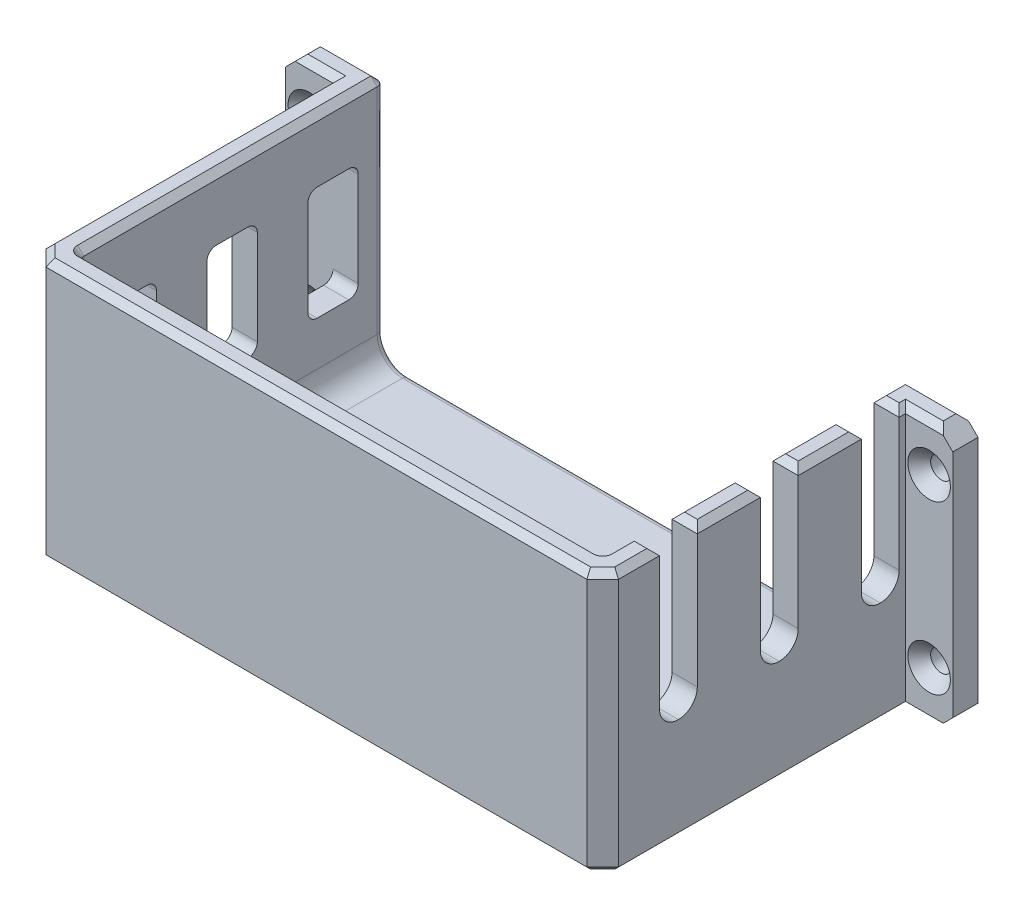
SolidWorks part; units mm, degrees
ref_plane "Front Plane" through (0, 0, 0) normal (0, 0, 1) x (1, 0, 0)
ref_plane "Top Plane" through (0, 0, 0) normal (0, 1, 0) x (1, 0, 0)
ref_plane "Right Plane" through (0, 0, 0) normal (1, 0, 0) x (0, 0, -1)
sketch "Sketch1" plane through (0, 0, 0) normal (0, 1, 0) x (1, 0, 0)
  line L0 (0, 0) -> (-23, 0)
  line L1 (-23, 0) -> (-23, -8)
  line L2 (-23, -8) -> (-8, -8)
  line L3 (-8, -8) -> (-8, -104)
  line L4 (-8, -104) -> (173.5, -104)
  line L5 (173.5, -104) -> (173.5, -8)
  line L6 (173.5, -8) -> (188.5, -8)
  line L7 (188.5, -8) -> (188.5, 0)
  line L8 (188.5, 0) -> (165.5, 0)
  line L9 (165.5, 0) -> (165.5, -96)
  line L10 (165.5, -96) -> (0, -96)
  line L11 (0, -96) -> (0, 0)
  line L12 (165.5, -96) -> (173.5, -96) construction
  line L13 (0, -96) -> (-8, -96) construction
  point P13 (170.5, -72.739)
  dimension "D1" = 8
  dimension "D2" = 165.5
  dimension "D3" = 8
  dimension "D4" = 15
  dimension "D5" = 8
  dimension "D6" = 96
extrude "Boss-Extrude1" add sketch "Sketch1" along normal blind 78
sketch "Sketch2" plane through (0, 0, 0) normal (0, -1, 0) x (1, 0, 0)
  line L0 (-23, 0) -> (188.5, 0)
  line L1 (188.5, 0) -> (188.5, 8)
  line L2 (188.5, 8) -> (173.5, 8)
  line L3 (173.5, 8) -> (173.5, 104)
  line L4 (173.5, 104) -> (-8, 104)
  line L5 (-8, 104) -> (-8, 8)
  line L6 (-8, 8) -> (-23, 8)
  line L7 (-23, 8) -> (-23, 0)
extrude "Boss-Extrude2" add sketch "Sketch2" along normal blind 5
sketch "Sketch4" plane through (0, 78, 0) normal (0, 1, 0) x (1, 0, 0)
  line L0 (0, 0) -> (0, -32) construction
  line L1 (0, -96) -> (0, 0) construction
  line L2 (0, -32) -> (0, -64) construction
  line L3 (0, -96) -> (0, 0) construction
  line L4 (0, -64) -> (0, -96) construction
  line L5 (0, -8) -> (-8, -8)
  line L6 (-8, -8) -> (-8, -104) construction
  line L7 (-8, -8) -> (-8, -24)
  line L8 (-8, -24) -> (0, -24)
  line L9 (0, -24) -> (0, -8)
  line L10 (-8, -40) -> (0, -40)
  line L11 (0, -40) -> (0, -56)
  line L12 (0, -56) -> (-8, -56)
  line L13 (-8, -56) -> (-8, -40)
  line L14 (-8, -72) -> (0, -72)
  line L15 (0, -72) -> (0, -88)
  line L16 (0, -88) -> (-8, -88)
  line L17 (-8, -88) -> (-8, -72)
  line L18 (0, -16) -> (165.5, -16) construction
  line L19 (165.5, 0) -> (165.5, -96) construction
  line L20 (0, -48) -> (165.5, -48) construction
  line L21 (165.5, 0) -> (165.5, -96) construction
  line L22 (0, -80) -> (165.5, -80) construction
  line L23 (165.5, -10) -> (165.5, -22)
  line L24 (165.5, -42) -> (165.5, -54)
  line L25 (165.5, -54) -> (173.5, -54)
  line L26 (173.5, -104) -> (173.5, -8) construction
  line L27 (173.5, -54) -> (173.5, -42)
  line L28 (173.5, -42) -> (165.5, -42)
  line L29 (165.5, -74) -> (165.5, -86)
  line L30 (165.5, -86) -> (173.5, -86)
  line L31 (173.5, -86) -> (173.5, -74)
  line L32 (173.5, -74) -> (165.5, -74)
  line L33 (165.5, -22) -> (173.5, -22)
  line L34 (173.5, -22) -> (173.5, -10)
  line L35 (173.5, -10) -> (165.5, -10)
  point P23 (0, -48)
  point P25 (0, -16)
  point P26 (0, -80)
  point P47 (0, 0)
  line M22 (173.5, -104) -> (173.5, -8)
  line M26 (165.5, 0) -> (165.5, -96)
  dimension "D1" = 32
  dimension "D2" = 16
  dimension "D3" = 12
extrude "Cut-Extrude1" cut sketch "Sketch4" against normal blind 36 from offset 20 contours L5 L7 L8 L9 | L13 L10 L11 L12 | L17 L14 L15 L16 offset against normal yes
extrude "Cut-Extrude2" cut sketch "Sketch4<5>" against normal blind 50 contours L28 L25 M22 M26 | L32 L30 M22 M26 | L35 L23 L33 L34 region at (169.5, 78, 48) region at (169.5, 78, 80)
sketch "Sketch4<5>" plane through (0, 78, 0) normal (0, 1, 0) x (1, 0, 0) same geometry as "Sketch4"
sketch "Sketch5" plane through (0, 0, 8) normal (0, 0, 1) x (1, 0, 0)
  line L0 (181, 78) -> (181, -5) construction
  line L1 (173.5, 78) -> (188.5, 78) construction
  line L2 (188.5, -5) -> (173.5, -5) construction
  line L3 (188.5, 36.5) -> (181, 36.5) construction
  line L4 (188.5, 78) -> (188.5, -5) construction
  point P6 (181, 63)
  point P12 (181, 10)
  dimension "D1" = 15
hole_wizard "CSK for 1/4 Flat Head Socket Cap Screw1" positions "Sketch5" profile "Sketch6" countersink size "1/4" standard "ANSI Inch" end condition through all
sketch "Sketch6" plane through (181, 10, 8) normal (1, 0, 0) x (0, -1, 0)
  line L0 (0, 0) -> (0, 8)
  line L1 (0, 8) -> (3.3782, 8)
  line L2 (3.3782, 8) -> (3.3782, 3.8716)
  line L3 (3.3782, 3.8716) -> (6.7437, 0)
  line L5 (6.7437, 0) -> (0, 0)
  line L6 (-3.3782, 3.8716) -> (-6.7437, 0) construction
  line L11 (0, -6.35) -> (0, 107.95) construction
  dimension "Thru Hole Dia." = 6.7564
  dimension "Thru Hole Depth" = 8
  dimension "Near C'Sink Dia." = 13.4874
  dimension "Near C'Sink Angle" = 82
ref_plane "Plane1" through (82.75, 0, 0) normal (1, 0, 0) x (0, 0, -1)
mirror "Mirror1" about plane through (82.75, 0, 0) normal (1, 0, 0) of "CSK for 1/4 Flat Head Socket Cap Screw1"
fillet "Fillet1" radius 3 12 edges at (-4, 22, 88) (-4, 22, 56) (-4, 22, 72) (-4, 22, 40) (-4, 58, 40) (-4, 58, 72) (-4, 58, 88) (-4, 58, 56) (-4, 58, 24) (-4, 58, 8) (-4, 22, 8) (-4, 22, 24)
fillet "Fillet2" radius 6 6 edges at (169.5, 28, 74) (169.5, 28, 42) (169.5, 28, 86) (169.5, 28, 54) (169.5, 28, 22) (169.5, 28, 10)
fillet "Fillet4" radius 8 2 edges at (0, 0, 48) (165.5, 0, 48)
fillet "Fillet3" radius 2 5 edges at (165.5, 43, 0) (0, 43, 0) (163.1569, 2.3431, 0) (82.75, 0, 0) (2.3431, 2.3431, 0)
fillet "Fillet5" radius 1 5 edges at (165.5, 43, 96) (163.1569, 2.3431, 96) (0, 43, 96) (2.3431, 2.3431, 96) (82.75, 0, 96)
chamfer "Chamfer1" distance 5 angle 45 6 edges at (173.5, 36.5, 104) (-8, 36.5, 104) (-23, 78, 4) (-23, -5, 4) (188.5, -5, 4) (188.5, 78, 4)
chamfer "Chamfer2" distance 2 angle 45 36 edges at (82.75, -5, 0) (178.5, -5, 8) (173.5, -5, 53.5) (171, -5, 101.5) (82.75, -5, 104) (-5.5, -5, 101.5) (-13, -5, 8) (-8, -5, 53.5) (173.5, 78, 9) (178.5, 78, 8) (173.5, 78, 32) (165.5, 78, 32) (165.5, 78, 64) (173.5, 78, 64) (165.5, 78, 6) (175.5, 78, 0) (173.5, 78, 92.5) (171, 78, 101.5) (82.75, 78, 104) (-5.5, 78, 101.5) (-8, 78, 53.5) (-13, 78, 8) (165.5, 78, 90.5) (82.75, 78, 96) (-10, 78, 0) (0, 78, 48.5) (169.5, 78, 22) (169.5, 78, 42) (169.5, 78, 54) (169.5, 78, 74) (169.5, 78, 10) (169.5, 78, 86) (166.0858, 78, 0.5858) (-0.5858, 78, 0.5858) (165.2071, 78, 95.7071) (0.2929, 78, 95.7071)
